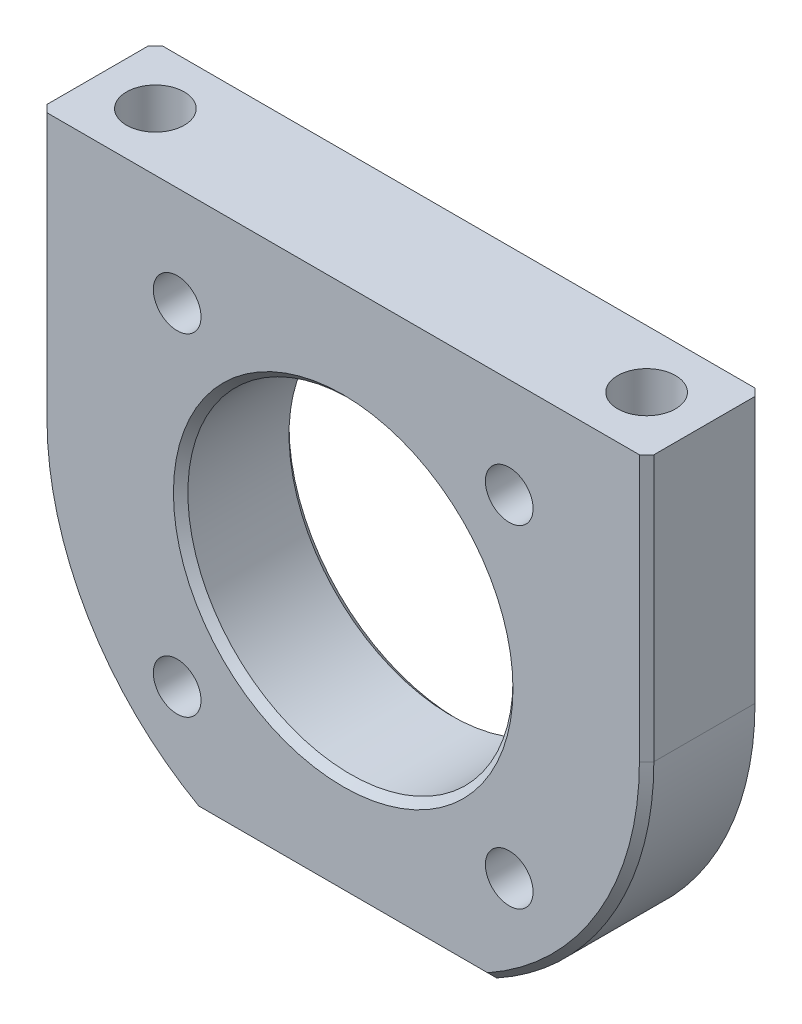
SolidWorks part; units mm, degrees
ref_plane "Front Plane" through (0, 0, 0) normal (0, 0, 1) x (1, 0, 0)
ref_plane "Top Plane" through (0, 0, 0) normal (0, 1, 0) x (1, 0, 0)
ref_plane "Right Plane" through (0, 0, 0) normal (1, 0, 0) x (0, 0, -1)
sketch "Sketch1" plane through (0, 0, 0) normal (0, 0, 1) x (1, 0, 0)
  line L0 (21, 0) -> (21, 18.4)
  line L3 (-10.1213, -18.4) -> (10.1213, -18.4)
  line L4 (-21, 0) -> (-21, 18.4)
  line L5 (-21, 18.4) -> (21, 18.4)
  arc A0 (10.1213, -18.4) -> (21, 0) centre (0, 0) ccw
  arc A1 (-21, 0) -> (-10.1213, -18.4) centre (0, 0) ccw
  dimension "D1" = 21
  dimension "D4" = 21
  dimension "D2" = 21
  dimension "D3" = 18.4
  dimension "D5" = 36.8
extrude "Boss-Extrude1" add sketch "Sketch1" along normal mid plane 8
sketch "Sketch2" plane through (0, 0, 4) normal (0, 0, 1) x (1, 0, 0)
  circle A0 centre (0, 0) radius 11.25
  dimension "D1" = 22.5
extrude "Cut-Extrude1" cut sketch "Sketch2" against normal through all
hole_wizard "M4x0.7 Tapped Hole3" positions "Sketch12" profile "Sketch11" tap size "M4x0.7" standard "ANSI Metric" end condition through all
sketch "Sketch12" plane through (0, 0, 4) normal (0, 0, 1) x (1, 0, 0)
  line L0 (-1000, 0) -> (49000, 0) construction
  line L1 (-707.1068, -707.1068) -> (34648.2323, 34648.2323) construction
  line L2 (-707.1068, 707.1068) -> (34648.2323, -34648.2323) construction
  circle A0 centre (0, 0) radius 16.25 construction
  point P0 (-11.4905, 11.4905)
  point P2 (11.4905, 11.4905)
  point P4 (11.4905, -11.4905)
  point P6 (-11.4905, -11.4905)
  dimension "D1" = 32.5
  dimension "D2" = 45
  dimension "D3" = 90
sketch "Sketch11" plane through (-11.4905, 11.4905, 4) normal (1, 0, 0) x (0, -1, 0)
  line L0 (0, 0) -> (0, 8)
  line L1 (0, 8) -> (1.65, 8)
  line L2 (1.65, 8) -> (1.65, 0)
  line L5 (1.65, 0) -> (0, 0)
  line L11 (0, -6.35) -> (0, 107.95) construction
  dimension "Thru Tap Drill Dia." = 3.3
  dimension "Thru Tap Drill Depth" = 8
cosmetic thread "Hole Thread7" parameters "D2"=4
cosmetic thread "Hole Thread8" parameters "D2"=4
cosmetic thread "Hole Thread9" parameters "D2"=4
cosmetic thread "Hole Thread10" parameters "D2"=4
hole_wizard "M4x0.7 Tapped Hole1" positions "Sketch8" profile "Sketch7" tap size "M4x0.7" standard "ANSI Metric"
sketch "Sketch8" plane through (0, 18.4, 0) normal (0, 1, 0) x (1, 0, 0)
  line L0 (-1000, 0) -> (49000, 0) construction
  point P0 (-17, 0)
  point P2 (17, 0)
  dimension "D1" = 17
  dimension "D2" = 17
cosmetic thread "Hole Thread1" parameters "D1"=7.3, "D2"=4
cosmetic thread "Hole Thread2" parameters "D1"=7.3, "D2"=4
sketch "Sketch7" plane through (-17, 18.4, 0) normal (1, 0, 0) x (0, 0, 1)
  line L0 (0, 0) -> (0, 8.9914)
  line L1 (0, 8.9914) -> (1.65, 8)
  line L2 (1.65, 8) -> (1.65, 0)
  line L5 (1.65, 0) -> (0, 0)
  line L10 (0, 8.9914) -> (-1.65, 8) construction
  line L11 (0, -6.35) -> (0, 107.95) construction
  dimension "Tap Drill Dia." = 3.3
  dimension "Tap Drill Depth" = 8
  dimension "Drill Angle" = 118
sketch "Sketch6" plane through (-3.375, 18.4, 0) normal (0, -1, 0) x (0, 0, -1)
  line L0 (0, -996.625) -> (0, 49003.375) construction
  circle A0 centre (0, -13.625) radius 2
  circle A1 centre (0, 20.375) radius 2
  dimension "D1" = 17
  dimension "D2" = 17
  dimension "D3" = 4
  dimension "D4" = 4
extrude "Cut-Extrude3" cut sketch "Sketch6" along normal blind 8
chamfer "Chamfer1" distance 0.5 angle 45 12 edges at (11.25, 0, -4) (-21, 9.2, 4) (-18.0769, -10.6877, 4) (0, -18.4, 4) (18.0769, -10.6877, 4) (21, 9.2, 4) (-21, 9.2, -4) (-18.0769, -10.6877, -4) (0, -18.4, -4) (18.0769, -10.6877, -4) (21, 9.2, -4) (11.25, 0, 4)
equation "\"D1@Sketch6\"=34/2"
equation "\"D4@Sketch6\"=\"D3@Sketch6\""
equation "\"D3@Sketch1\"=\"D5@Sketch1\"/2"
equation "\"D2@Sketch6\"=\"D1@Sketch6\""
